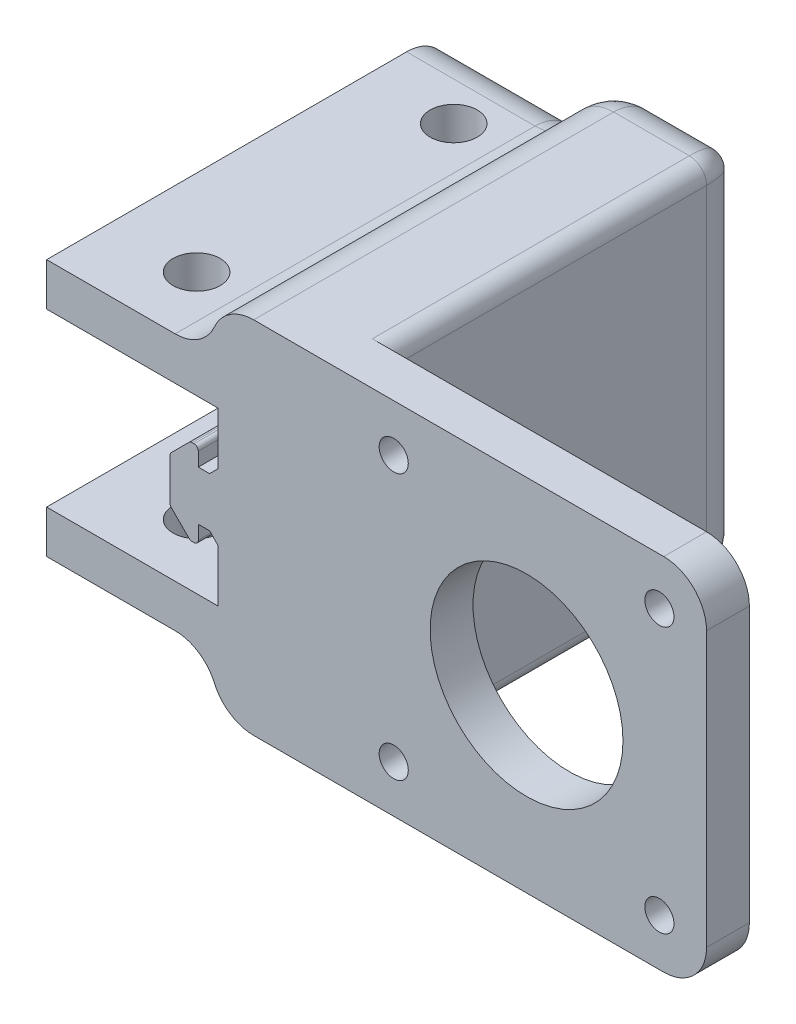
SolidWorks part; units mm, degrees
ref_plane "Front Plane" through (0, 0, 0) normal (0, 0, 1) x (1, 0, 0)
ref_plane "Top Plane" through (0, 0, 0) normal (0, 1, 0) x (1, 0, 0)
ref_plane "Right Plane" through (0, 0, 0) normal (1, 0, 0) x (0, 0, -1)
sketch "Sketch1" plane through (0, 0, 0) normal (0, 0, 1) x (1, 0, 0)
  line L1 (-21, -21) -> (21, -21)
  line L2 (-21, -21) -> (-21, 21)
  line L3 (-21, 21) -> (21, 21)
  line L4 (21, -21) -> (21, 21)
  line L5 (-21, -21) -> (21, 21) construction
  line L6 (-21, 21) -> (21, -21) construction
  point P0 (0, 0)
  dimension "D1" = 42
extrude "Boss-Extrude1" add sketch "Sketch1" along normal blind 5 contours L2 L3 L4 L1
sketch "Sketch2" plane through (0, 0, 5) normal (0, 0, 1) x (1, 0, 0)
  line L1 (15.5, 15.5) -> (-15.5, 15.5) construction
  line L2 (15.5, 15.5) -> (15.5, -15.5) construction
  line L3 (15.5, -15.5) -> (-15.5, -15.5) construction
  line L4 (-15.5, 15.5) -> (-15.5, -15.5) construction
  line L5 (15.5, 15.5) -> (-15.5, -15.5) construction
  line L6 (15.5, -15.5) -> (-15.5, 15.5) construction
  circle A0 centre (0, 0) radius 11.25
  dimension "D1" = 22.5
  dimension "D2" = 31
extrude "Cut-Extrude1" cut sketch "Sketch2" against normal up to next
hole_wizard "M3 Clearance Hole1" positions "3DSketch1" profile "Sketch3" hole size "M3" standard "ANSI Metric" end condition through all
sketch3d "3DSketch1"
  point P0 (15.5, 15.5, 5)
  point P3 (15.5, -15.5, 5)
  point P6 (-15.5, -15.5, 5)
  point P9 (-15.5, 15.5, 5)
sketch "Sketch3" plane through (15.5, 15.5, 5) normal (1, 0, 0) x (0, -1, 0)
  line L0 (0, 0) -> (0, 5)
  line L1 (0, 5) -> (1.7, 5)
  line L2 (1.7, 5) -> (1.7, 0)
  line L5 (1.7, 0) -> (0, 0)
  line L11 (0, -6.35) -> (0, 107.95) construction
  dimension "Thru Hole Dia." = 3.4
  dimension "Thru Hole Depth" = 5
sketch "Sketch4" plane through (0, 0, 5) normal (0, 0, 1) x (1, 0, 0)
  line L0 (-21, 21) -> (-36, 21)
  line L1 (-36, 21) -> (-36, 15)
  line L2 (-36, 15) -> (-56, 15)
  line L3 (-56, 15) -> (-56, 10)
  line L4 (-56, 10) -> (-36, 10)
  line L5 (-36, 10) -> (-36, 0)
  line L6 (-36, 0) -> (-21, 0)
  line L7 (-21, -21) -> (-21, 21) construction
  line L8 (-21, 21) -> (-21, 0)
  dimension "D2" = 15
  dimension "D3" = 10
  dimension "D4" = 5
  dimension "D5" = 20
extrude "Boss-Extrude2" add sketch "Sketch4" against normal offset from surface (45 mm away) 40 up to plane "Front Plane" offset beyond the face yes
mirror "Mirror1" about plane through (0, 0, 0) normal (0, 1, 0) of "Boss-Extrude2"
fillet "Fillet3" radius 5 2 edges at (21, -21, 2.5) (21, 21, 2.5)
fillet "Fillet4" radius 5 2 edges at (-36, -15, -17.5) (-36, 15, -17.5)
fillet "Fillet5" radius 5 2 edges at (-36, -21, -17.5) (-36, 21, -17.5)
sketch "Sketch5" plane through (0, -15, 0) normal (0, -1, 0) x (1, 0, 0)
  line L0 (-56, -17.5) -> (-46, -17.5) construction
  line L1 (-56, -40) -> (-56, 5) construction
  line L2 (-46, -2.5) -> (-46, -32.5) construction
  point P7 (-46, -17.5)
  dimension "D1" = 30
  dimension "10" = 10
hole_wizard "M5 Clearance Hole1" positions "3DSketch2" profile "Sketch6" hole size "M5" standard "ANSI Metric" end condition through all
sketch3d "3DSketch2"
  point P0 (-46, -15, -2.5)
  point P3 (-46, -15, -32.5)
sketch "Sketch6" plane through (-46, -15, -2.5) normal (1, 0, 0) x (0, 0, -1)
  line L0 (0, 0) -> (0, 36)
  line L1 (0, 36) -> (2.75, 36)
  line L2 (2.75, 36) -> (2.75, 0)
  line L5 (2.75, 0) -> (0, 0)
  line L11 (0, -6.35) -> (0, 107.95) construction
  dimension "Thru Hole Dia." = 5.5
  dimension "Thru Hole Depth" = 36
sketch "Sketch7" plane through (0, 0, -40) normal (0, 0, -1) x (-1, 0, 0)
  line L10 (21, -21) -> (31.8348, -21)
  line L11 (41, -15) -> (56, -15)
  line L12 (56, -15) -> (56, -10)
  line L13 (56, -10) -> (36, -10)
  line L14 (36, -10) -> (36, 10)
  line L15 (36, 10) -> (56, 10)
  line L16 (56, 10) -> (56, 15)
  line L17 (56, 15) -> (41, 15)
  line L18 (31.8348, 21) -> (21, 21)
  line L19 (21, 21) -> (21, -21)
  line L20 (21, -21) -> (31.8348, -21)
  line L21 (41, -15) -> (56, -15)
  line L26 (56, -15) -> (56, 15)
  line L27 (56, 15) -> (41, 15)
  line L28 (31.8348, 21) -> (21, 21)
  line L29 (21, 21) -> (21, -21)
  arc A4 (31.8348, -21) -> (36.4174, -18) centre (31.8348, -16) ccw
  arc A5 (41, -15) -> (36.4174, -18) centre (41, -20) ccw
  arc A6 (36.4174, 18) -> (41, 15) centre (41, 20) ccw
  arc A7 (36.4174, 18) -> (31.8348, 21) centre (31.8348, 16) ccw
  arc A8 (31.8348, -21) -> (36.4174, -18) centre (31.8348, -16) ccw
  arc A9 (41, -15) -> (36.4174, -18) centre (41, -20) ccw
  arc A10 (36.4174, 18) -> (41, 15) centre (41, 20) ccw
  arc A11 (36.4174, 18) -> (31.8348, 21) centre (31.8348, 16) ccw
  dimension "D1" = 0
extrude "Boss-Extrude3" add sketch "Sketch7" along normal blind 2
fillet "Fillet7" radius 2 2 edges at (-21, 21, -21) (-21, -21, -21)
fillet "Fillet8" radius 5 11 edges at (-48.5, 15, -42) (-38.2614, 15.8167, -42) (-34.5735, 20.1833, -42) (-27.4174, 21, -42) (-21.5858, 20.4142, -42) (-21, 0, -42) (-21.5858, -20.4142, -42) (-27.4174, -21, -42) (-48.5, -15, -42) (-38.2614, -15.8167, -42) (-34.5735, -20.1833, -42)
sketch "Sketch9" plane through (0, 0, -40) normal (0, 0, 1) x (1, 0, 0)
  line L0 (-37.19, -3.3865) -> (-36.2024, -4.3741) construction
  line L1 (-37.8, -3.3865) -> (-37.19, -3.3865) construction
  line L2 (-37.8, -5.5) -> (-37.8, -3.3865) construction
  line L3 (-39.439, -5.5) -> (-37.8, -5.5) construction
  line L4 (-42.0995, -2.8395) -> (-39.439, -5.5) construction
  line L5 (-42.0995, -0.1) -> (-42.0995, -2.8395) construction
  line L6 (-42.0995, 2.8395) -> (-42.0995, 0.1) construction
  line L7 (-39.439, 5.5) -> (-42.0995, 2.8395) construction
  line L8 (-37.8, 5.5) -> (-39.439, 5.5) construction
  line L9 (-37.8, 3.3865) -> (-37.8, 5.5) construction
  line L10 (-37.19, 3.3865) -> (-37.8, 3.3865) construction
  line L11 (-36.2024, 4.3741) -> (-37.19, 3.3865) construction
  line L12 (-37.19, -3.3865) -> (-36.2024, -4.3741) construction
  line L13 (-37.8, -3.3865) -> (-37.19, -3.3865) construction
  line L14 (-37.8, -5.5) -> (-37.8, -3.3865) construction
  line L15 (-39.439, -5.5) -> (-37.8, -5.5) construction
  line L16 (-42.0995, -2.8395) -> (-39.439, -5.5) construction
  line L17 (-42.0995, -0.1) -> (-42.0995, -2.8395) construction
  line L18 (-42.0995, 2.8395) -> (-42.0995, 0.1) construction
  line L19 (-39.439, 5.5) -> (-42.0995, 2.8395) construction
  line L20 (-37.8, 5.5) -> (-39.439, 5.5) construction
  line L21 (-37.8, 3.3865) -> (-37.8, 5.5) construction
  line L22 (-37.19, 3.3865) -> (-37.8, 3.3865) construction
  line L23 (-36.2024, 4.3741) -> (-37.19, 3.3865) construction
  line L24 (-36, 3.8694) -> (-36.9829, 2.8865)
  line L25 (-36.9829, 2.8865) -> (-38.3, 2.8865)
  line L26 (-38.3, 2.8865) -> (-38.3, 5)
  line L27 (-38.3, 5) -> (-39.2319, 5)
  line L28 (-39.2319, 5) -> (-41.5995, 2.6324)
  line L29 (-41.5995, 2.6324) -> (-41.5995, 0.1)
  line L30 (-41.5995, 0.1) -> (-41.5995, -2.6324)
  line L31 (-41.5995, -2.6324) -> (-39.2319, -5)
  line L32 (-39.2319, -5) -> (-38.3, -5)
  line L33 (-38.3, -5) -> (-38.3, -2.8865)
  line L34 (-38.3, -2.8865) -> (-36.9829, -2.8865)
  line L35 (-36.9829, -2.8865) -> (-36, -3.8694)
  line L36 (-41.5995, -0.1) -> (-41.5995, -2.6324) construction
  line L37 (-36, -3.8694) -> (-36, 3.8694)
  line L38 (-36, -10) -> (-36, 10) construction
  line L41 (-36.9829, -2.8865) -> (-35.8489, -4.0205) construction
  line L43 (-35.8489, 4.0205) -> (-36.9829, 2.8865) construction
  arc A0 (-36, -4.8628) -> (-36.2024, -4.3741) centre (-36.6912, -4.8628) ccw construction
  arc A1 (-36.2024, 4.3741) -> (-36, 4.8628) centre (-36.6912, 4.8628) ccw construction
  arc A2 (-36, -4.8628) -> (-36.2024, -4.3741) centre (-36.6912, -4.8628) ccw construction
  arc A3 (-36.2024, 4.3741) -> (-36, 4.8628) centre (-36.6912, 4.8628) ccw construction
  dimension "D1" = 0.5
extrude "Boss-Extrude5" add sketch "Sketch9" along normal up to surface (45 mm away) up to face at (17.2, 15.5, 5)
fillet "Fillet10" radius 0.5 6 edges at (-39.2319, -5, -17.5) (-38.3, -5, -17.5) (-41.5995, -2.6324, -17.5) (-41.5995, 2.6324, -17.5) (-39.2319, 5, -17.5) (-38.3, 5, -17.5)
sketch "Sketch10" plane through (0, 0, -42) normal (0, 0, -1) x (-1, 0, 0)
  line L0 (56, 0) -> (46, 0) construction
  line L1 (56, -10) -> (56, 10) construction
  dimension "D1" = 10
hole_wizard "M5 Clearance Hole2" positions "3DSketch3" profile "Sketch11" hole size "M5" standard "ANSI Metric" end condition through all
sketch3d "3DSketch3"
  point P0 (-46, 0, -42)
sketch "Sketch11" plane through (-46, 0, -42) normal (1, 0, 0) x (0, 1, 0)
  line L0 (0, 0) -> (0, 47)
  line L1 (0, 47) -> (2.75, 47)
  line L2 (2.75, 47) -> (2.75, 0)
  line L5 (2.75, 0) -> (0, 0)
  line L11 (0, -6.35) -> (0, 107.95) construction
  dimension "Thru Hole Dia." = 5.5
  dimension "Thru Hole Depth" = 47
